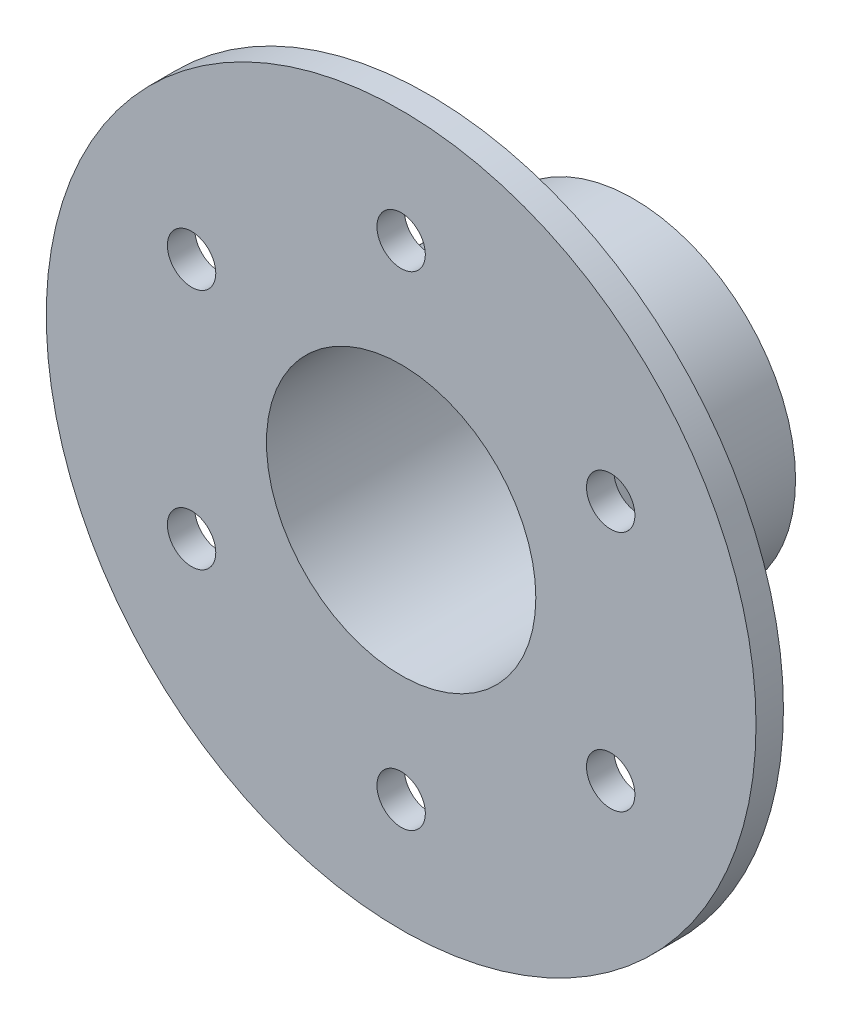
SolidWorks part; units mm, degrees
material "PVC Rígido"
ref_plane "Alzado" through (0, 0, 0) normal (0, 0, 1) x (1, 0, 0)
ref_plane "Planta" through (0, 0, 0) normal (0, 1, 0) x (1, 0, 0)
ref_plane "Vista lateral" through (0, 0, 0) normal (1, 0, 0) x (0, 0, -1)
sketch "Croquis1" plane through (0, 0, 0) normal (0, 0, 1) x (1, 0, 0)
  circle A0 centre (0, 0) radius 16.7
  circle A1 centre (0, 0) radius 20.1
  dimension "D1" = 33.4
  dimension "D2" = 40.2
extrude "Saliente-Extruir1" add sketch "Croquis1" along normal blind 25.4
sketch "Croquis2" plane through (0, 0, 25.4) normal (0, 0, 1) x (1, 0, 0)
  line L0 (0, 0) -> (0, 30) construction
  circle A0 centre (0, 0) radius 16.7
  circle A1 centre (0, 0) radius 44
  circle A3 centre (0, 30) radius 3
  circle A9 centre (25.9808, 15) radius 3
  circle A10 centre (25.9808, -15) radius 3
  circle A11 centre (0, -30) radius 3
  circle A12 centre (-25.9808, -15) radius 3
  circle A13 centre (-25.9808, 15) radius 3
  point P18 (0, 0)
  dimension "D1" = 33.4
  dimension "D2" = 88
  dimension "D3" = 30
  dimension "D4" = 6
  dimension "D5" = 6
extrude "Saliente-Extruir2" add sketch "Croquis2" along normal blind 3.4
